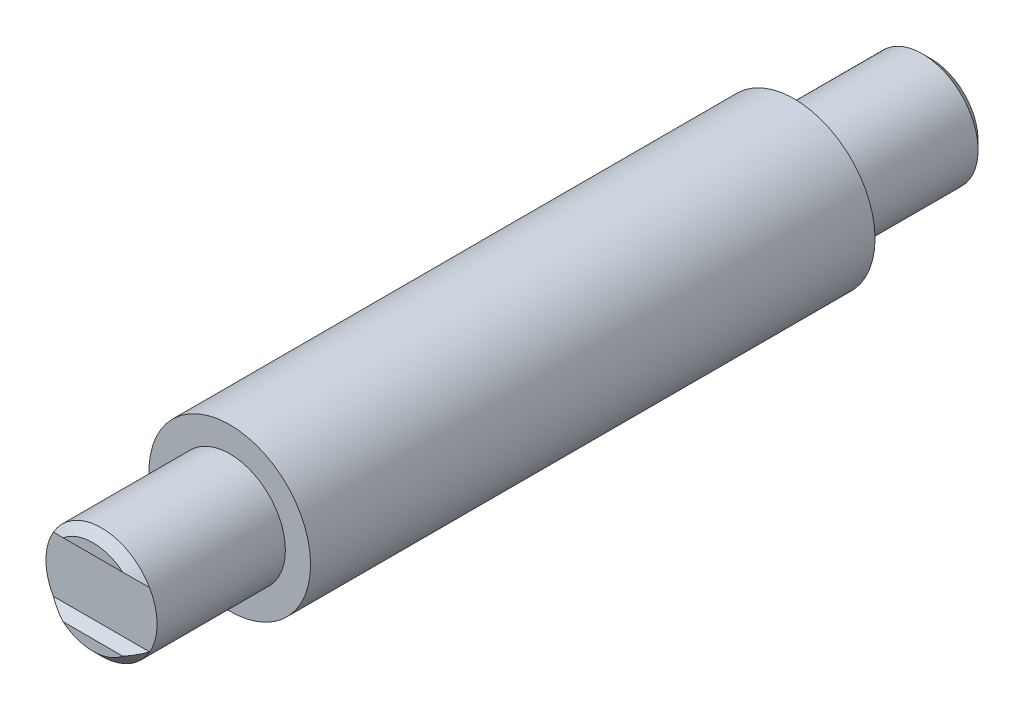
SolidWorks part; units mm, degrees
ref_plane "Alzado" through (0, 0, 0) normal (0, 0, 1) x (1, 0, 0)
ref_plane "Planta" through (0, 0, 0) normal (0, 1, 0) x (1, 0, 0)
ref_plane "Vista lateral" through (0, 0, 0) normal (1, 0, 0) x (0, 0, -1)
sketch "Croquis1" plane through (0, 0, 0) normal (0, 0, 1) x (1, 0, 0)
  circle A0 centre (0, 0) radius 9.45
  dimension "D1" = 18.9
extrude "Saliente-Extruir1" add sketch "Croquis1" along normal blind 66
sketch "Croquis7" plane through (0, 0, 0) normal (0, 0, -1) x (-1, 0, 0)
  circle A0 centre (0, 0) radius 6.5
  dimension "D1" = 13
extrude "Saliente-Extruir5" add sketch "Croquis7" along normal blind 16
chamfer "Chaflán5" distance 1 angle 45 1 edges at (-6.5, 0, -16)
sketch "Croquis12" plane through (0, 0, 66) normal (0, 0, 1) x (1, 0, 0)
  circle A0 centre (0, 0) radius 6.5
  dimension "D1" = 13
extrude "Saliente-Extruir6" add sketch "Croquis12" along normal blind 16
sketch "Croquis13" plane through (0, 0, 82) normal (0, 0, 1) x (1, 0, 0)
  line L0 (0, 0) -> (5.7663, -0.1869) construction
  line L1 (5.7663, -3) -> (-5.7663, -3)
  line L3 (5.7663, 3) -> (-5.7663, 3)
  circle A0 centre (0, 0) radius 6.5 construction
  arc A1 (-5.7663, -3) -> (-5.7663, 3) centre (0, 0) cw
  arc A2 (5.7663, -3) -> (5.7663, 3) centre (0, 0) ccw
  point P0 (0, 0)
  dimension "D1" = 6
extrude "Cortar-Extruir12" cut sketch "Croquis13" against normal blind 1
chamfer "Chaflán7" distance 1.25 angle 45 1 edges at (0, 3, 82)
chamfer "Chaflán8" distance 1.25 angle 45 1 edges at (0, -3, 82)
chamfer "Chaflán9" distance 1 angle 45 1 edges at (0, 6.5, 82)
chamfer "Chaflán10" distance 1 angle 45 1 edges at (0, -6.5, 82)
